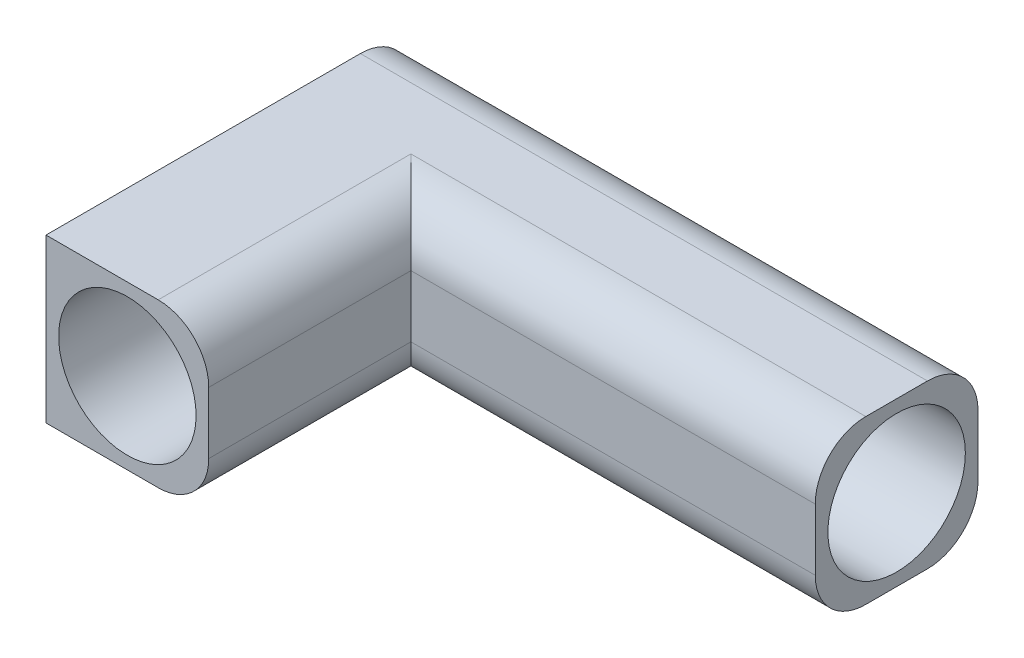
SolidWorks part; units mm, degrees
ref_plane "Front Plane" through (0, 0, 0) normal (0, 0, 1) x (1, 0, 0)
ref_plane "Top Plane" through (0, 0, 0) normal (0, 1, 0) x (1, 0, 0)
ref_plane "Right Plane" through (0, 0, 0) normal (1, 0, 0) x (0, 0, -1)
sketch "Sketch2" plane through (0, 0, 0) normal (0, 1, 0) x (1, 0, 0)
  line L0 (0, 0) -> (0, 72.2)
  line L1 (0, 72.2) -> (112.2, 72.2)
  line L2 (112.2, 72.2) -> (112.2, 40)
  line L3 (112.2, 40) -> (32.2, 40)
  line L4 (32.2, 40) -> (32.2, 0)
  line L5 (32.2, 0) -> (0, 0)
  dimension "D1" = 40
  dimension "D2" = 32.2
  dimension "D3" = 80
extrude "Boss-Extrude1" add sketch "Sketch2" along normal blind 32.2
sketch "Sketch3" plane through (0, 0, 0) normal (0, 0, 1) x (1, 0, 0)
  line L0 (0, 0) -> (32.2, 32.2) construction
  circle A0 centre (16.1, 16.1) radius 13.6
  dimension "D1" = 27.2
extrude "Cut-Extrude1" cut sketch "Sketch3" against normal through all
sketch "Sketch4" plane through (112.2, 0, 0) normal (1, 0, 0) x (0, 0, -1)
  line L0 (40, 32.2) -> (72.2, 0) construction
  circle A0 centre (56.1, 16.1) radius 13.6
  dimension "D1" = 27.2
extrude "Cut-Extrude2" cut sketch "Sketch4" against normal through all
fillet "Fillet1" radius 10 6 edges at (56.1, 0, -72.2) (56.1, 32.2, -72.2) (72.2, 32.2, -40) (72.2, 0, -40) (32.2, 0, -20) (32.2, 32.2, -20)
